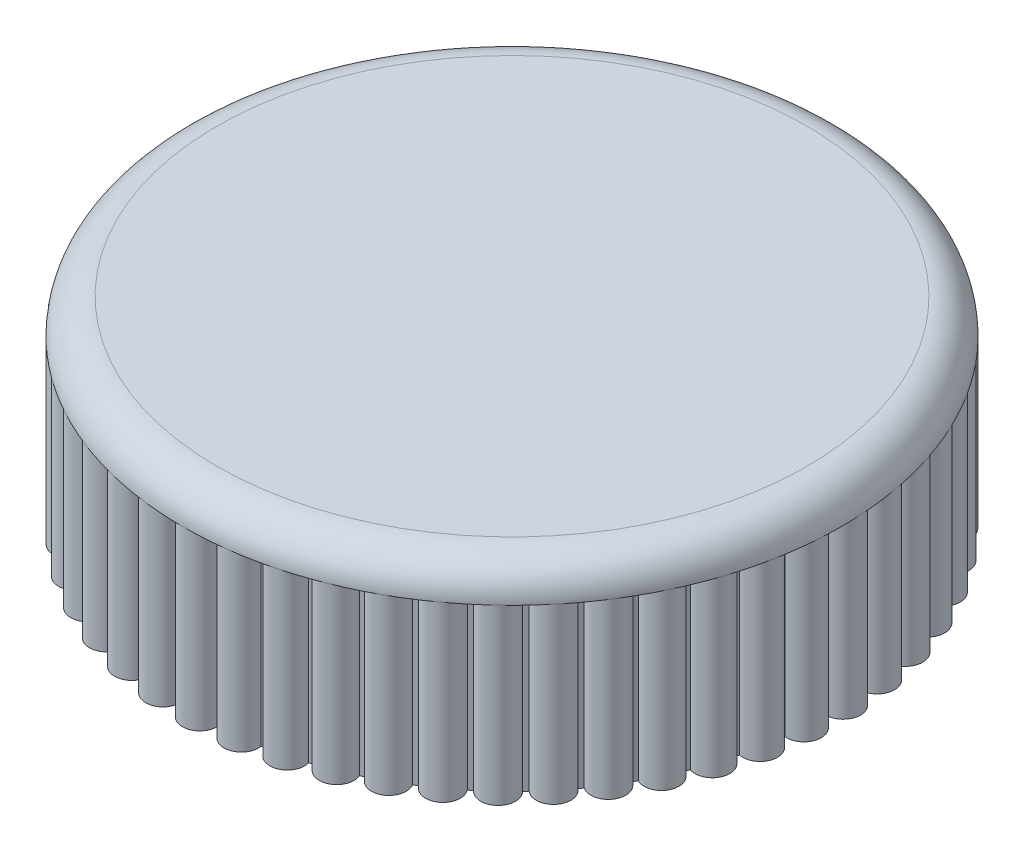
SolidWorks part; units mm, degrees
material "PET"
ref_plane "Front Plane" through (0, 0, 0) normal (0, 0, 1) x (1, 0, 0)
ref_plane "Top Plane" through (0, 0, 0) normal (0, 1, 0) x (1, 0, 0)
ref_plane "Right Plane" through (0, 0, 0) normal (1, 0, 0) x (0, 0, -1)
sketch "Sketch1" plane through (0, 0, 0) normal (0, 1, 0) x (1, 0, 0)
  line L0 (0, 0) -> (0, 15.4578) construction
  arc A0 (-0.4998, 8.9861) -> (-0.6304, 8.9779) centre (0, 0) ccw
  arc A2 (0.4998, 8.9861) -> (-0.4998, 8.9861) centre (0, 9) ccw
  arc A3 (1.6221, 8.8526) -> (0.6304, 8.9779) centre (1.128, 8.929) ccw
  arc A4 (2.7189, 8.5795) -> (1.7507, 8.8281) centre (2.2382, 8.7172) ccw
  arc A5 (3.7727, 8.1711) -> (2.8433, 8.5391) centre (3.3131, 8.368) ccw
  arc A6 (4.7671, 7.6338) -> (3.8911, 8.1154) centre (4.3358, 7.8868) ccw
  arc A7 (5.6863, 6.9761) -> (4.8776, 7.5637) centre (5.2901, 7.2812) ccw
  arc A8 (6.5158, 6.2085) -> (5.7871, 6.8927) centre (6.1609, 6.5607) ccw
  arc A9 (7.2425, 5.3429) -> (6.6053, 6.1131) centre (6.9346, 5.7368) ccw
  arc A10 (7.855, 4.393) -> (7.3194, 5.237) centre (7.599, 4.8224) ccw
  arc A11 (8.3437, 3.3739) -> (7.9181, 4.2783) centre (8.1434, 3.832) ccw
  arc A12 (8.7007, 2.3015) -> (8.3919, 3.2522) centre (8.5595, 2.7812) ccw
  arc A13 (8.9206, 1.1929) -> (8.7333, 2.1748) centre (8.8406, 1.6864) ccw
  arc A14 (8.9998, 0.0654) -> (8.937, 1.0631) centre (8.9822, 0.5651) ccw
  arc A15 (8.937, -1.0631) -> (8.9998, -0.0654) centre (8.9822, -0.5651) ccw
  arc A16 (8.7333, -2.1748) -> (8.9206, -1.1929) centre (8.8406, -1.6864) ccw
  arc A17 (8.3919, -3.2522) -> (8.7007, -2.3015) centre (8.5595, -2.7812) ccw
  arc A18 (7.9181, -4.2783) -> (8.3437, -3.3739) centre (8.1434, -3.832) ccw
  arc A19 (7.3194, -5.237) -> (7.855, -4.393) centre (7.599, -4.8224) ccw
  arc A20 (6.6053, -6.1131) -> (7.2425, -5.3429) centre (6.9346, -5.7368) ccw
  arc A21 (5.7871, -6.8927) -> (6.5158, -6.2085) centre (6.1609, -6.5607) ccw
  arc A22 (4.8776, -7.5637) -> (5.6863, -6.9761) centre (5.2901, -7.2812) ccw
  arc A23 (3.8911, -8.1154) -> (4.7671, -7.6338) centre (4.3358, -7.8868) ccw
  arc A24 (2.8433, -8.5391) -> (3.7727, -8.1711) centre (3.3131, -8.368) ccw
  arc A25 (1.7507, -8.8281) -> (2.7189, -8.5795) centre (2.2382, -8.7172) ccw
  arc A26 (0.6304, -8.9779) -> (1.6221, -8.8526) centre (1.128, -8.929) ccw
  arc A27 (-0.4998, -8.9861) -> (0.4998, -8.9861) centre (0, -9) ccw
  arc A28 (-1.6221, -8.8526) -> (-0.6304, -8.9779) centre (-1.128, -8.929) ccw
  arc A29 (-2.7189, -8.5795) -> (-1.7507, -8.8281) centre (-2.2382, -8.7172) ccw
  arc A30 (-3.7727, -8.1711) -> (-2.8433, -8.5391) centre (-3.3131, -8.368) ccw
  arc A31 (-4.7671, -7.6338) -> (-3.8911, -8.1154) centre (-4.3358, -7.8868) ccw
  arc A32 (-5.6863, -6.9761) -> (-4.8776, -7.5637) centre (-5.2901, -7.2812) ccw
  arc A33 (-6.5158, -6.2085) -> (-5.7871, -6.8927) centre (-6.1609, -6.5607) ccw
  arc A34 (-7.2425, -5.3429) -> (-6.6053, -6.1131) centre (-6.9346, -5.7368) ccw
  arc A35 (-7.855, -4.393) -> (-7.3194, -5.237) centre (-7.599, -4.8224) ccw
  arc A36 (-8.3437, -3.3739) -> (-7.9181, -4.2783) centre (-8.1434, -3.832) ccw
  arc A37 (-8.7007, -2.3015) -> (-8.3919, -3.2522) centre (-8.5595, -2.7812) ccw
  arc A38 (-8.9206, -1.1929) -> (-8.7333, -2.1748) centre (-8.8406, -1.6864) ccw
  arc A39 (-8.9998, -0.0654) -> (-8.937, -1.0631) centre (-8.9822, -0.5651) ccw
  arc A40 (-8.937, 1.0631) -> (-8.9998, 0.0654) centre (-8.9822, 0.5651) ccw
  arc A41 (-8.7333, 2.1748) -> (-8.9206, 1.1929) centre (-8.8406, 1.6864) ccw
  arc A42 (-8.3919, 3.2522) -> (-8.7007, 2.3015) centre (-8.5595, 2.7812) ccw
  arc A43 (-7.9181, 4.2783) -> (-8.3437, 3.3739) centre (-8.1434, 3.832) ccw
  arc A44 (-7.3194, 5.237) -> (-7.855, 4.393) centre (-7.599, 4.8224) ccw
  arc A45 (-6.6053, 6.1131) -> (-7.2425, 5.3429) centre (-6.9346, 5.7368) ccw
  arc A46 (-5.7871, 6.8927) -> (-6.5158, 6.2085) centre (-6.1609, 6.5607) ccw
  arc A47 (-4.8776, 7.5637) -> (-5.6863, 6.9761) centre (-5.2901, 7.2812) ccw
  arc A48 (-3.8911, 8.1154) -> (-4.7671, 7.6338) centre (-4.3358, 7.8868) ccw
  arc A49 (-2.8433, 8.5391) -> (-3.7727, 8.1711) centre (-3.3131, 8.368) ccw
  arc A50 (-1.7507, 8.8281) -> (-2.7189, 8.5795) centre (-2.2382, 8.7172) ccw
  arc A51 (-0.6304, 8.9779) -> (-1.6221, 8.8526) centre (-1.128, 8.929) ccw
  arc A52 (0.6304, 8.9779) -> (0.4998, 8.9861) centre (0, 0) ccw
  arc A53 (2.8433, 8.5391) -> (2.7189, 8.5795) centre (0, 0) ccw
  arc A54 (1.7507, 8.8281) -> (1.6221, 8.8526) centre (0, 0) ccw
  arc A55 (3.8911, 8.1154) -> (3.7727, 8.1711) centre (0, 0) ccw
  arc A56 (4.8776, 7.5637) -> (4.7671, 7.6338) centre (0, 0) ccw
  arc A57 (5.7871, 6.8927) -> (5.6863, 6.9761) centre (0, 0) ccw
  arc A58 (6.6053, 6.1131) -> (6.5158, 6.2085) centre (0, 0) ccw
  arc A59 (7.3194, 5.237) -> (7.2425, 5.3429) centre (0, 0) ccw
  arc A60 (7.9181, 4.2783) -> (7.855, 4.393) centre (0, 0) ccw
  arc A61 (8.3919, 3.2522) -> (8.3437, 3.3739) centre (0, 0) ccw
  arc A62 (8.7333, 2.1748) -> (8.7007, 2.3015) centre (0, 0) ccw
  arc A63 (8.937, 1.0631) -> (8.9206, 1.1929) centre (0, 0) ccw
  arc A64 (8.9998, -0.0654) -> (8.9998, 0.0654) centre (0, 0) ccw
  arc A65 (8.9206, -1.1929) -> (8.937, -1.0631) centre (0, 0) ccw
  arc A66 (8.7007, -2.3015) -> (8.7333, -2.1748) centre (0, 0) ccw
  arc A67 (8.3437, -3.3739) -> (8.3919, -3.2522) centre (0, 0) ccw
  arc A68 (7.855, -4.393) -> (7.9181, -4.2783) centre (0, 0) ccw
  arc A69 (7.2425, -5.3429) -> (7.3194, -5.237) centre (0, 0) ccw
  arc A70 (6.5158, -6.2085) -> (6.6053, -6.1131) centre (0, 0) ccw
  arc A71 (5.6863, -6.9761) -> (5.7871, -6.8927) centre (0, 0) ccw
  arc A72 (4.7671, -7.6338) -> (4.8776, -7.5637) centre (0, 0) ccw
  arc A73 (3.7727, -8.1711) -> (3.8911, -8.1154) centre (0, 0) ccw
  arc A74 (2.7189, -8.5795) -> (2.8433, -8.5391) centre (0, 0) ccw
  arc A75 (1.6221, -8.8526) -> (1.7507, -8.8281) centre (0, 0) ccw
  arc A76 (0.4998, -8.9861) -> (0.6304, -8.9779) centre (0, 0) ccw
  arc A77 (-0.6304, -8.9779) -> (-0.4998, -8.9861) centre (0, 0) ccw
  arc A78 (-1.7507, -8.8281) -> (-1.6221, -8.8526) centre (0, 0) ccw
  arc A79 (-2.8433, -8.5391) -> (-2.7189, -8.5795) centre (0, 0) ccw
  arc A80 (-3.8911, -8.1154) -> (-3.7727, -8.1711) centre (0, 0) ccw
  arc A81 (-4.8776, -7.5637) -> (-4.7671, -7.6338) centre (0, 0) ccw
  arc A82 (-5.7871, -6.8927) -> (-5.6863, -6.9761) centre (0, 0) ccw
  arc A83 (-6.6053, -6.1131) -> (-6.5158, -6.2085) centre (0, 0) ccw
  arc A84 (-7.3194, -5.237) -> (-7.2425, -5.3429) centre (0, 0) ccw
  arc A85 (-7.9181, -4.2783) -> (-7.855, -4.393) centre (0, 0) ccw
  arc A86 (-8.3919, -3.2522) -> (-8.3437, -3.3739) centre (0, 0) ccw
  arc A87 (-8.7333, -2.1748) -> (-8.7007, -2.3015) centre (0, 0) ccw
  arc A88 (-2.7189, 8.5795) -> (-2.8433, 8.5391) centre (0, 0) ccw
  arc A89 (-1.6221, 8.8526) -> (-1.7507, 8.8281) centre (0, 0) ccw
  arc A90 (-3.7727, 8.1711) -> (-3.8911, 8.1154) centre (0, 0) ccw
  arc A91 (-4.7671, 7.6338) -> (-4.8776, 7.5637) centre (0, 0) ccw
  arc A92 (-5.6863, 6.9761) -> (-5.7871, 6.8927) centre (0, 0) ccw
  arc A93 (-6.5158, 6.2085) -> (-6.6053, 6.1131) centre (0, 0) ccw
  arc A94 (-7.2425, 5.3429) -> (-7.3194, 5.237) centre (0, 0) ccw
  arc A95 (-7.855, 4.393) -> (-7.9181, 4.2783) centre (0, 0) ccw
  arc A96 (-8.3437, 3.3739) -> (-8.3919, 3.2522) centre (0, 0) ccw
  arc A97 (-8.7007, 2.3015) -> (-8.7333, 2.1748) centre (0, 0) ccw
  arc A98 (-8.9206, 1.1929) -> (-8.937, 1.0631) centre (0, 0) ccw
  arc A99 (-8.9998, 0.0654) -> (-8.9998, -0.0654) centre (0, 0) ccw
  arc A100 (-8.937, -1.0631) -> (-8.9206, -1.1929) centre (0, 0) ccw
  point P157 (0, 0)
  dimension "D1" = 18
  dimension "D3" = 1
  dimension "D4" = 50
extrude "Boss-Extrude1" add sketch "Sketch1" along normal blind 5
sketch "Sketch2" plane through (0, 5, 0) normal (0, 1, 0) x (1, 0, 0)
  circle A0 centre (0, 0) radius 9.5
  dimension "D1" = 19
extrude "Boss-Extrude2" add sketch "Sketch2" along normal blind 1
fillet "Fillet1" radius 1 1 edges at (0, 6, 9.5)
sketch "Sketch3" plane through (0, 0, 0) normal (0, -1, 0) x (1, 0, 0)
  circle A0 centre (0, 0) radius 7.5
  dimension "D1" = 15
extrude "Cut-Extrude1" cut sketch "Sketch3" against normal blind 4
